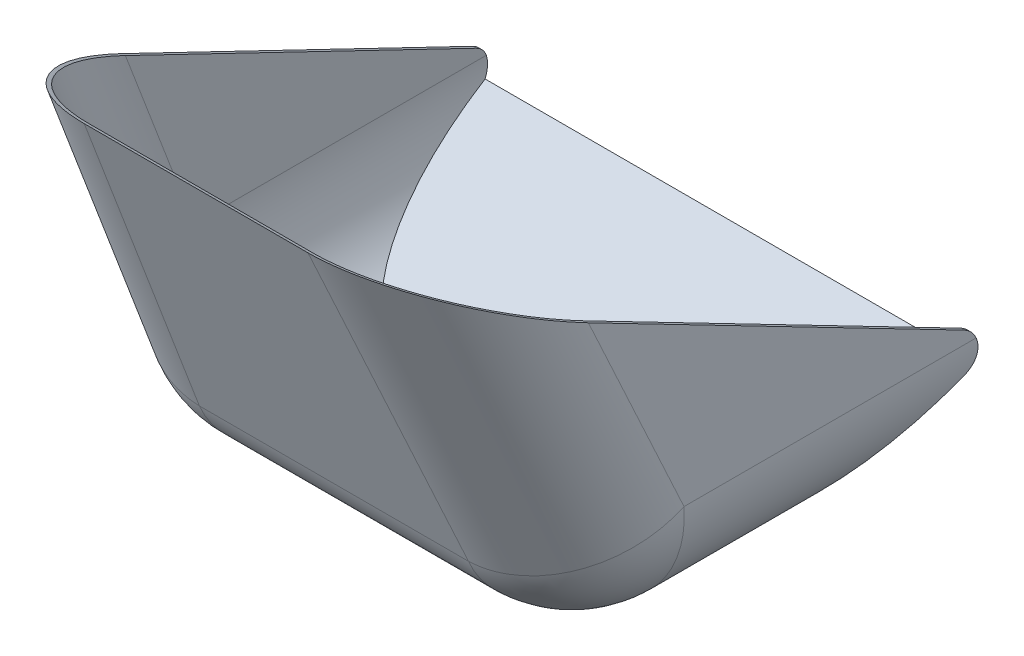
SolidWorks part; units mm, degrees
ref_plane "Front Plane" through (0, 0, 0) normal (0, 0, 1) x (1, 0, 0)
ref_plane "Top Plane" through (0, 0, 0) normal (0, 1, 0) x (1, 0, 0)
ref_plane "Right Plane" through (0, 0, 0) normal (1, 0, 0) x (0, 0, -1)
sketch "Sketch2" plane through (0, 0, 0) normal (0, 0, 1) x (1, 0, 0)
  line L0 (-227, 0) -> (227, 0)
  line L1 (227, 0) -> (202.5256, 350)
  line L2 (202.5256, 350) -> (-202.5256, 350)
  line L3 (0, 350) -> (0, 0)
  line L4 (-227, 0) -> (-202.5256, 350)
  dimension "D1" = 227
  dimension "D2" = 86
  dimension "D3" = 350
extrude "Boss-Extrude1" add sketch "Sketch2" along normal blind 500 contours L4 L0 L3 L2 | L2 L3 L0 L1 region at (-107.4976, 171.6762, 0) region at (107.4976, 171.6762, 0)
sketch "Sketch3" plane through (0, 0, 0) normal (1, 0, 0) x (0, 0, -1)
  line L0 (-500, 350) -> (-334.2868, -40.3958)
  line L1 (-334.2868, -40.3958) -> (-621.9678, -40.3958)
  line L2 (-621.9678, -40.3958) -> (-621.9678, 481.5706)
  line L3 (-621.9678, 481.5706) -> (-512.7984, 425.1037)
  line L4 (-512.7984, 425.1037) -> (-500, 350)
  line L5 (-500, 0) -> (-500, 350) construction
  line L6 (-500, 350) -> (45.7452, 77.1274)
  line L7 (45.7452, 77.1274) -> (101.1899, 520.959)
  line L8 (101.1899, 520.959) -> (-512.7984, 425.1037)
  line L9 (0, 0) -> (0, 100) construction
  line L10 (0, 0) -> (0, 350) construction
  dimension "D1" = 23
  dimension "D2" = 100
extrude "Cut-Extrude1" cut sketch "Sketch3" against normal through all both and the other way through all contours L4 L3 L2 L1 L0 | L7 L8 L4 L6 region at (0, 163.5308, 521.1216) region at (0, 334.0506, 146.6154)
fillet "Fillet1" radius 100 2 edges at (214.7628, 175, 425.7169) (-214.7628, 175, 425.7169)
fillet "Fillet2" radius 100 5 edges at (227, 0, 119.9184) (-227, 0, 119.9184) (-196.6665, 0, 318.561) (0, 0, 351.4338) (196.6665, 0, 318.561)
sketch "Sketch4" plane through (0, 0, 0) normal (1, 0, 0) x (0, 0, -1)
  line L0 (0, 100) -> (-190.3287, 0)
  line L1 (0, 0) -> (-285.2453, 0) construction
  line L2 (-190.3287, 0) -> (0, 0)
  line L3 (0, 0) -> (0, 100)
  dimension "D1" = 215
extrude "Cut-Extrude2" cut sketch "Sketch4" against normal through all both and the other way through all contours L2 L3 L0 region at (0, 33.3333, 63.4429)
shell "Shell1" thickness 3 removed face at (0, 212.6743, 225.3486)
fillet "Fillet3" radius 20 1 edges at (0, 100, 0)
